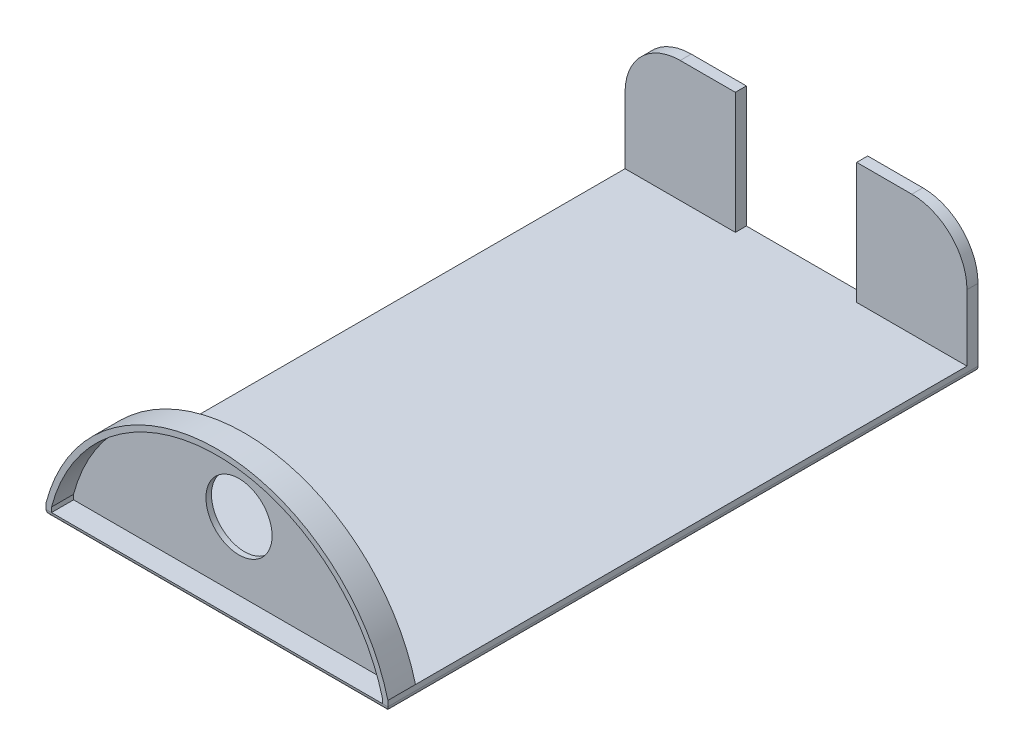
SolidWorks part; units mm, degrees
ref_plane "Front Plane" through (0, 0, 0) normal (0, 0, 1) x (1, 0, 0)
ref_plane "Top Plane" through (0, 0, 0) normal (0, 1, 0) x (1, 0, 0)
ref_plane "Right Plane" through (0, 0, 0) normal (1, 0, 0) x (0, 0, -1)
sketch "Sketch3" plane through (0, 0, 0) normal (0, 0, 1) x (1, 0, 0)
  line L0 (0, 0) -> (0, 24)
  line L1 (0, 24) -> (20, 24)
  line L2 (20, 24) -> (20, 2)
  line L3 (20, 2) -> (42, 2)
  line L4 (42, 2) -> (42, 24)
  line L5 (42, 24) -> (62, 24)
  line L6 (62, 24) -> (62, 0)
  line L7 (62, 0) -> (0, 0)
  dimension "D1" = 20
  dimension "D2" = 20
  dimension "D3" = 62
  dimension "D4" = 22
  dimension "D5" = 24
  dimension "D6" = 24
extrude "Boss-Extrude1" add sketch "Sketch3" along normal blind 2
sketch "Sketch4" plane through (0, 0, 2) normal (0, 0, 1) x (1, 0, 0)
  line L0 (62, 0) -> (62, 24) construction
  line L1 (0, 0) -> (62, 0)
  line L2 (0, 0) -> (0, 2)
  line L3 (0, 2) -> (62, 2)
  line L4 (62, 0) -> (62, 2)
extrude "Boss-Extrude2" add sketch "Sketch4" along normal blind 100
sketch "Sketch6" plane through (0, 0, 102) normal (0, 0, 1) x (1, 0, 0)
  line L0 (0, 2) -> (0, 0)
  line L1 (0, 0) -> (62, 0)
  line L2 (62, 0) -> (62, 2)
  arc A0 (0, 2) -> (62, 2) centre (31, -6.0235) cw
extrude "Boss-Extrude3" add sketch "Sketch6" along normal blind 5
shell "Shell1" thickness 1 removed face at (31, 6.9995, 107)
fillet "Fillet1" radius 1 3 edges at (31, 0, 107) (62, 0, 53.5) (0, 0, 53.5)
sketch "Sketch7" plane through (0, 0, 103) normal (0, 0, 1) x (1, 0, 0)
  circle A0 centre (31, 13.3435) radius 6
  dimension "D1" = 12
extrude "Cut-Extrude1" cut sketch "Sketch7" against normal blind 2
fillet "Fillet2" radius 10 1 edges at (0, 24, 1)
fillet "Fillet3" radius 10 1 edges at (62, 24, 1)
